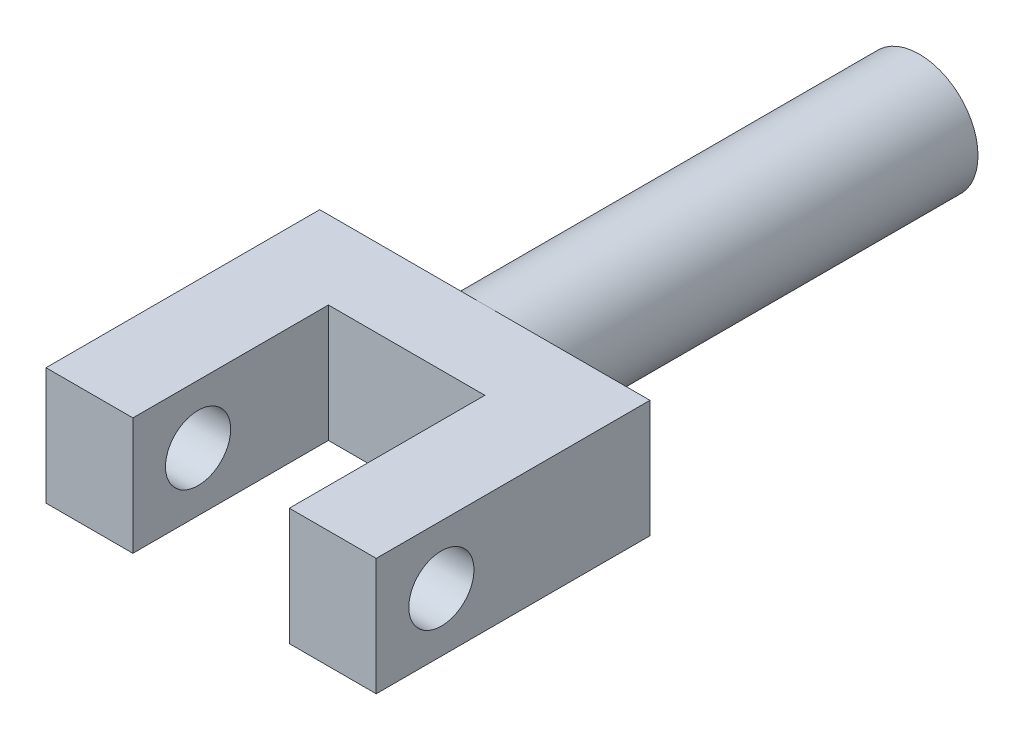
SolidWorks part; units mm, degrees
ref_plane "Front Plane" through (0, 0, 0) normal (0, 0, 1) x (1, 0, 0)
ref_plane "Top Plane" through (0, 0, 0) normal (0, 1, 0) x (1, 0, 0)
ref_plane "Right Plane" through (0, 0, 0) normal (1, 0, 0) x (0, 0, -1)
sketch "Sketch1" plane through (0, 0, 0) normal (0, 0, 1) x (1, 0, 0)
  circle A0 centre (0, 0) radius 1.35
  dimension "D1" = 2.7
extrude "Boss-Extrude1" add sketch "Sketch1" along normal blind 10
sketch "Sketch3" plane through (0, 0, 0) normal (0, 1, 0) x (1, 0, 0)
  line L5 (0, -10) -> (-3.8, -10)
  line L6 (-1.35, -10) -> (1.35, -10) construction
  line L12 (-3.8, -10) -> (-3.8, -16.3)
  line L13 (-3.8, -16.3) -> (-1.8, -16.3)
  line L14 (-1.8, -16.3) -> (-1.8, -11.8)
  line L15 (-1.8, -11.8) -> (1.8, -11.8)
  line L16 (1.8, -11.8) -> (1.8, -16.3)
  line L17 (1.8, -16.3) -> (3.8, -16.3)
  line L18 (3.8, -16.3) -> (3.8, -10)
  line L19 (3.8, -10) -> (0, -10)
  dimension "D1" = 4.5
  dimension "D2" = 4.5
  dimension "D3" = 1.8
  dimension "D4" = 1.8
  dimension "D5" = 1.8
  dimension "D6" = 2
  dimension "D7" = 2
extrude "Boss-Extrude5" add sketch "Sketch3" along normal blind 1.35 and the other way blind 1.35
sketch "Sketch4" plane through (-1.8, 0, 0) normal (1, 0, 0) x (0, 0, -1)
  line L0 (-16.3, -1.35) -> (-16.3, 1.35) construction
  line L1 (-16.3, 1.35) -> (-11.8, 1.35) construction
  circle A0 centre (-14.8, 0) radius 0.75
  dimension "D1" = 1.5
  dimension "D3" = 1.5
  dimension "D2" = 1.35
extrude "Cut-Extrude1" cut sketch "Sketch4" against normal blind 11.25 and the other way blind 11.25
